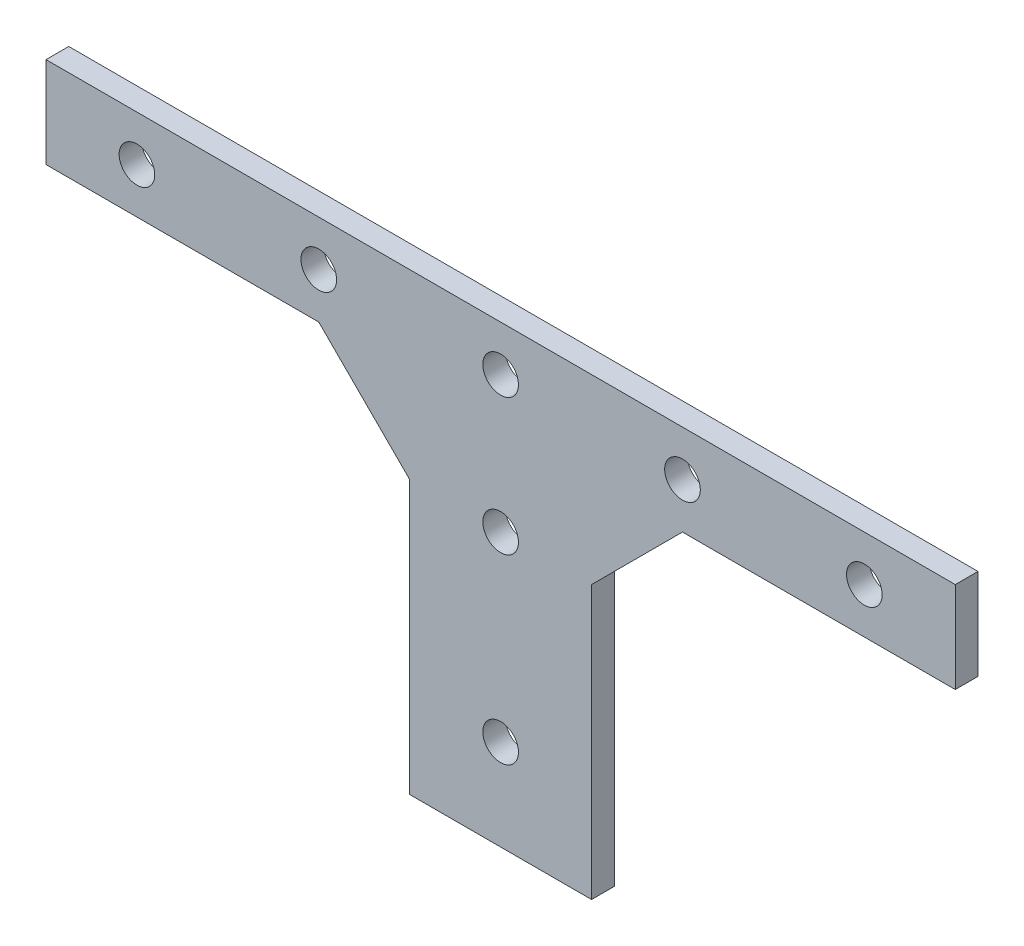
SolidWorks part; units mm, degrees
ref_plane "Front Plane" through (0, 0, 0) normal (0, 0, 1) x (1, 0, 0)
ref_plane "Top Plane" through (0, 0, 0) normal (0, 1, 0) x (1, 0, 0)
ref_plane "Right Plane" through (0, 0, 0) normal (1, 0, 0) x (0, 0, -1)
sketch "Sketch1" plane through (0, 0, 0) normal (0, 0, 1) x (1, 0, 0)
  line L0 (41.275, -25.4) -> (41.275, -63.5)
  line L2 (41.275, -63.5) -> (66.675, -63.5)
  line L4 (66.675, -63.5) -> (66.675, -25.4)
  line L5 (79.375, -12.7) -> (117.475, -12.7)
  line L7 (117.475, -12.7) -> (117.475, 0)
  line L9 (117.475, 0) -> (-9.525, 0)
  line L10 (-9.525, 0) -> (-9.525, -12.7)
  line L11 (-9.525, -12.7) -> (28.575, -12.7)
  line L13 (66.675, -25.4) -> (79.375, -12.7)
  line L14 (53.975, -12.7) -> (53.975, -25.4) construction
  line L15 (41.275, -25.4) -> (28.575, -12.7)
  line L16 (53.975, -63.5) -> (53.975, 0) construction
  line L17 (117.475, -6.35) -> (-9.525, -6.35) construction
  line L18 (117.475, -6.35) -> (104.775, -6.35) construction
  line L19 (104.775, -6.35) -> (79.375, -6.35) construction
  line L20 (79.375, -6.35) -> (53.975, -6.35) construction
  line L21 (53.975, -6.35) -> (28.575, -6.35) construction
  line L22 (28.575, -6.35) -> (3.175, -6.35) construction
  line L23 (53.975, -25.4) -> (53.975, -50.8) construction
  dimension "D3" = 127
extrude "Boss-Extrude1" add sketch "Sketch1" along normal blind 3.175
hole_wizard "#10 Clearance Hole1" positions "Sketch4" profile "Sketch5" hole size "#10" standard "ANSI Inch" end condition through all
sketch "Sketch4" plane through (0, 0, 3.175) normal (0, 0, 1) x (1, 0, 0)
  point P0 (3.175, -6.35)
  point P3 (28.575, -6.35)
  point P6 (53.975, -6.35)
  point P13 (104.775, -6.35)
  point P16 (53.975, -25.4)
  point P19 (53.975, -50.8)
  point P22 (79.375, -6.35)
sketch "Sketch5" plane through (3.175, -6.35, 3.175) normal (1, 0, 0) x (0, -1, 0)
  line L0 (0, 0) -> (0, 3.175)
  line L1 (0, 3.175) -> (2.4892, 3.175)
  line L2 (2.4892, 3.175) -> (2.4892, 0)
  line L5 (2.4892, 0) -> (0, 0)
  line L11 (0, -6.35) -> (0, 107.95) construction
  dimension "Thru Hole Dia." = 4.9784
  dimension "Thru Hole Depth" = 3.175
